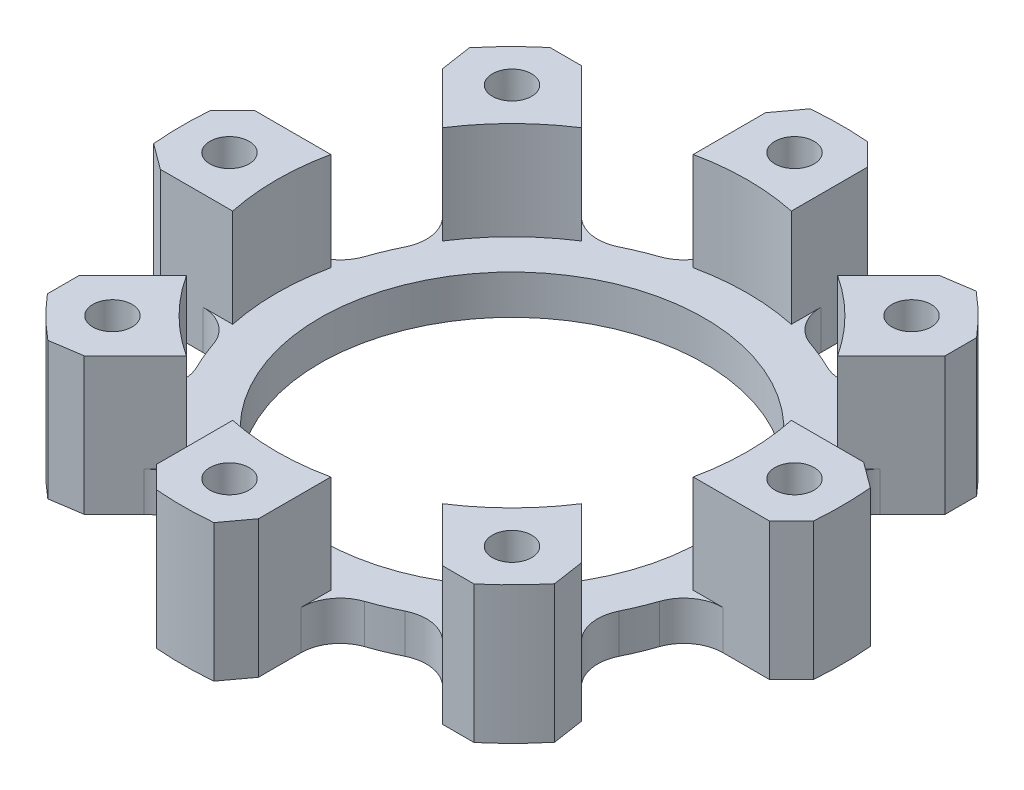
SolidWorks part; units mm, degrees
material "Nylon 101"
ref_plane "Front" through (0, 0, 0) normal (0, 0, 1) x (1, 0, 0)
ref_plane "Top" through (0, 0, 0) normal (0, 1, 0) x (1, 0, 0)
ref_plane "Right" through (0, 0, 0) normal (1, 0, 0) x (0, 0, -1)
sketch "Sketch1" plane through (0, 0, 0) normal (0, 1, 0) x (1, 0, 0)
  circle A0 centre (0, 0) radius 38.1
  dimension "D1" = 76.2
extrude "Base Extrude" add sketch "Sketch1" along normal blind 6.35
sketch "Sketch2" plane through (0, 0, 0) normal (0, 1, 0) x (1, 0, 0)
  line L0 (-7.9375, 37.264) -> (-7.9375, 52.7461)
  line L1 (7.9375, 37.264) -> (7.9375, 52.7461)
  circle A0 centre (0, 0) radius 45.72 construction
  circle A1 centre (0, 0) radius 38.1 construction
  arc A2 (7.9375, 37.264) -> (-7.9375, 37.264) centre (0, 0) ccw
  arc A4 (7.9375, 52.7461) -> (-7.9375, 52.7461) centre (0, 0) ccw
  circle A5 centre (0, 0) radius 53.34 construction
  point P5 (0, 38.1)
  dimension "D1" = 91.44
  dimension "D2" = 7.62
  dimension "D3" = 15.875
extrude "Column" add sketch "Sketch2" along normal blind 22.225
sketch "Sketch3" plane through (0, 0, 0) normal (0, 1, 0) x (1, 0, 0)
  circle A0 centre (0, 45.72) radius 3.175
  circle A1 centre (0, 0) radius 45.72 construction
  dimension "D1" = 91.44
  dimension "D2" = 6.35
extrude "Fastener Hole Cut" cut sketch "Sketch3" along normal through all
fillet "Relief Fillet" radius 6.35 2 edges at (-7.9375, 3.175, -37.264) (7.9375, 3.175, -37.264)
chamfer "Cosmetic Chamfer" distance 3.175 angle 45 2 edges at (7.9375, 11.1125, -52.7461) (-7.9375, 11.1125, -52.7461) first distance on face at (7.9375, 9.525, -44.0338) first distance on face at (0, 11.1125, -53.0431)
pattern_circular "Column and Hole Pattern" count 8 over 360 about axis through (0, 0, 0) along (0, 1, 0) of "Cosmetic Chamfer", "Column", "Fastener Hole Cut", "Relief Fillet"
sketch "Sketch4" plane through (0, 0, 0) normal (0, 1, 0) x (1, 0, 0)
  circle A0 centre (0, 0) radius 31.115
  dimension "D1" = 62.23
extrude "Access Hole Cut" cut sketch "Sketch4" along normal through all
sketch "Sketch7" plane through (0, 0, 0) normal (0, 1, 0) x (1, 0, 0)
  circle A0 centre (0, 45.72) radius 4.7625
  dimension "D1" = 9.525
extrude "Counter Bore Cut" cut sketch "Sketch7" along normal blind 6.604
pattern_circular "Counter Bore Pattern" count 8 over 360 about axis through (0, 6.35, 0) along (0, -1, 0) of "Counter Bore Cut"
